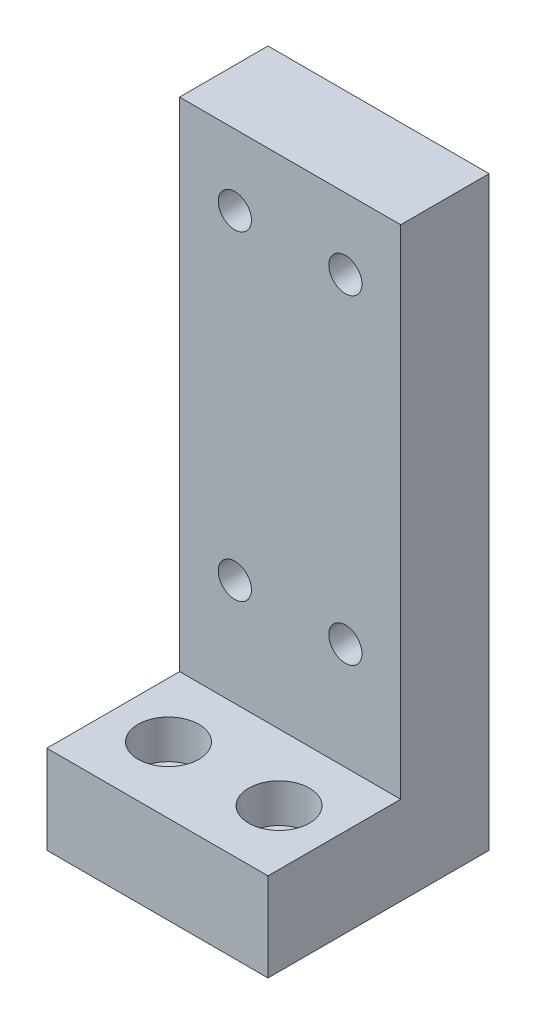
SolidWorks part; units mm, degrees
ref_plane "Front Plane" through (0, 0, 0) normal (0, 0, 1) x (1, 0, 0)
ref_plane "Top Plane" through (0, 0, 0) normal (0, 1, 0) x (1, 0, 0)
ref_plane "Right Plane" through (0, 0, 0) normal (1, 0, 0) x (0, 0, -1)
sketch "Sketch1" plane through (0, 0, 0) normal (0, 0, 1) x (1, 0, 0)
  line L1 (0, 0) -> (-20, 0)
  line L2 (0, 0) -> (0, 45)
  line L3 (0, 45) -> (-20, 45)
  line L4 (-20, 0) -> (-20, 45)
  dimension "D1" = 20
  dimension "D2" = 45
extrude "Boss-Extrude1" add sketch "Sketch1" along normal blind 8
sketch "Sketch2" plane through (0, 0, 8) normal (0, 0, 1) x (1, 0, 0)
  circle A0 centre (-15, 38.6) radius 1.5
  circle A1 centre (-5, 38.6) radius 1.5
  circle A2 centre (-15, 9.65) radius 1.5
  circle A3 centre (-5, 9.65) radius 1.5
  dimension "D1" = 3
extrude "Cut-Extrude1" cut sketch "Sketch2" against normal up to surface (8 mm away) up to face at (-10, 22.5, 0)
sketch "Sketch3" plane through (0, 0, 0) normal (0, 0, -1) x (-1, 0, 0)
  circle A0 centre (5, 38.6) radius 2.75
  circle A1 centre (15, 38.6) radius 2.75
  circle A2 centre (5, 9.65) radius 2.75
  circle A3 centre (15, 9.65) radius 2.75
  dimension "D1" = 5.5
extrude "Cut-Extrude2" cut sketch "Sketch3" against normal blind 3.3
sketch "Sketch4" plane through (0, 0, 0) normal (0, -1, 0) x (1, 0, 0)
  line L0 (-20, 0) -> (0, 0)
  line L1 (0, 0) -> (0, 20)
  line L2 (0, 20) -> (-20, 20)
  line L3 (-20, 20) -> (-20, 0)
extrude "Boss-Extrude2" add sketch "Sketch4" along normal blind 8
sketch "Sketch5" plane through (0, 0, 0) normal (0, 1, 0) x (1, 0, 0)
  line L0 (-20, -14) -> (0, -14) construction
  line L1 (-20, -20) -> (-20, -8) construction
  line L2 (0, -8) -> (0, -20) construction
  line L3 (-20, -14) -> (-15, -20) construction
  line L4 (0, -20) -> (-20, -20) construction
  line L5 (-15, -20) -> (-10, -14) construction
  line L6 (-10, -14) -> (-5, -20) construction
  line L7 (-5, -20) -> (0, -14) construction
  line L8 (-15, -20) -> (-15, -14) construction
  line L9 (-5, -20) -> (-5, -14) construction
  circle A0 centre (-15, -14) radius 1.5
  circle A1 centre (-5, -14) radius 1.5
  dimension "D1" = 3
extrude "Cut-Extrude3" cut sketch "Sketch5" against normal up to surface (8 mm away) up to face at (-10, -8, 10)
sketch "Sketch6" plane through (0, 0, 0) normal (0, 1, 0) x (1, 0, 0)
  circle A0 centre (-15, -14) radius 2.75
  circle A1 centre (-5, -14) radius 2.75
  dimension "D1" = 5.5
extrude "Cut-Extrude4" cut sketch "Sketch6" against normal blind 3.5
